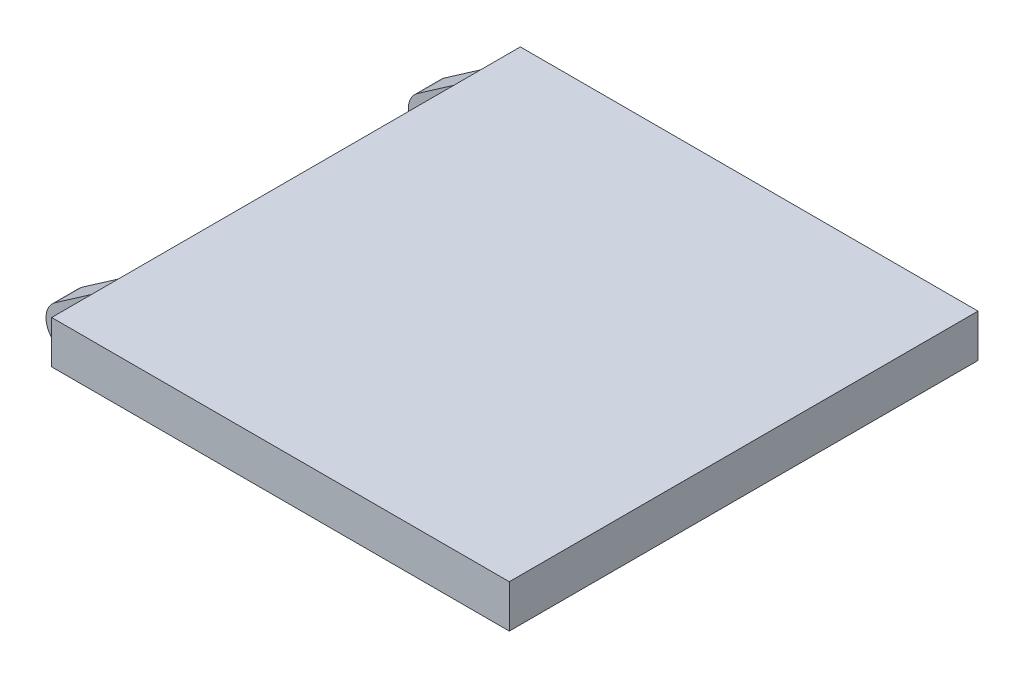
SolidWorks part; units mm, degrees
ref_plane "Front Plane" through (0, 0, 0) normal (0, 0, 1) x (1, 0, 0)
ref_plane "Top Plane" through (0, 0, 0) normal (0, 1, 0) x (1, 0, 0)
ref_plane "Right Plane" through (0, 0, 0) normal (1, 0, 0) x (0, 0, -1)
sketch "Sketch1" plane through (0, 0, 0) normal (0, 1, 0) x (1, 0, 0)
  line L1 (42.7791, -43.812) -> (-42.7791, -43.812)
  line L2 (42.7791, -43.812) -> (42.7791, 43.812)
  line L3 (42.7791, 43.812) -> (-42.7791, 43.812)
  line L4 (-42.7791, -43.812) -> (-42.7791, 43.812)
  line L5 (42.7791, -43.812) -> (-42.7791, 43.812) construction
  line L6 (42.7791, 43.812) -> (-42.7791, -43.812) construction
  point P0 (0, 0)
extrude "Boss-Extrude1" add sketch "Sketch1" along normal blind 8
sketch "Sketch2" plane through (0, 0, 36.97) normal (0, 0, -1) x (-1, 0, 0)
  line L2 (42.7791, 0) -> (42.7791, 8)
  line L3 (42.7791, 0) -> (43.2791, 0)
  line L4 (42.7791, 8) -> (49.5623, 3.2843)
  arc A1 (44.9959, 3.2843) -> (51.2791, 0) centre (47.2791, 0) ccw construction
  arc A2 (43.2791, 0) -> (49.5623, 3.2843) centre (47.2791, 0) ccw
extrude "Boss-Extrude2" add sketch "Sketch2" along normal blind 5 from offset 0.6 separate body
sketch "Sketch3" plane through (0, 0, 36.97) normal (0, 0, -1) x (-1, 0, 0)
  circle A0 centre (47.2791, 0) radius 2
  arc A1 (43.2791, 0) -> (49.5623, 3.2843) centre (47.2791, 0) ccw construction
  dimension "D1" = 4
extrude "Boss-Extrude3" add sketch "Sketch3" along normal blind 3.8 draft 14 separate body
fillet "Fillet1" radius 1 1 edges at (-48.3317, 0, 33.17)
combine bodies "Combine1" operation type subtract main body 102 bodies to subtract 103
surface "reduce to 0.1 if too loose" parameters "D1"=0.4
ref_plane "Plane1" through (0, 0, 0) normal (0, 0, -1) x (-1, 0, 0)
mirror "Mirror1" about plane through (0, 0, 0) normal (0, 0, -1) of bodies 104
